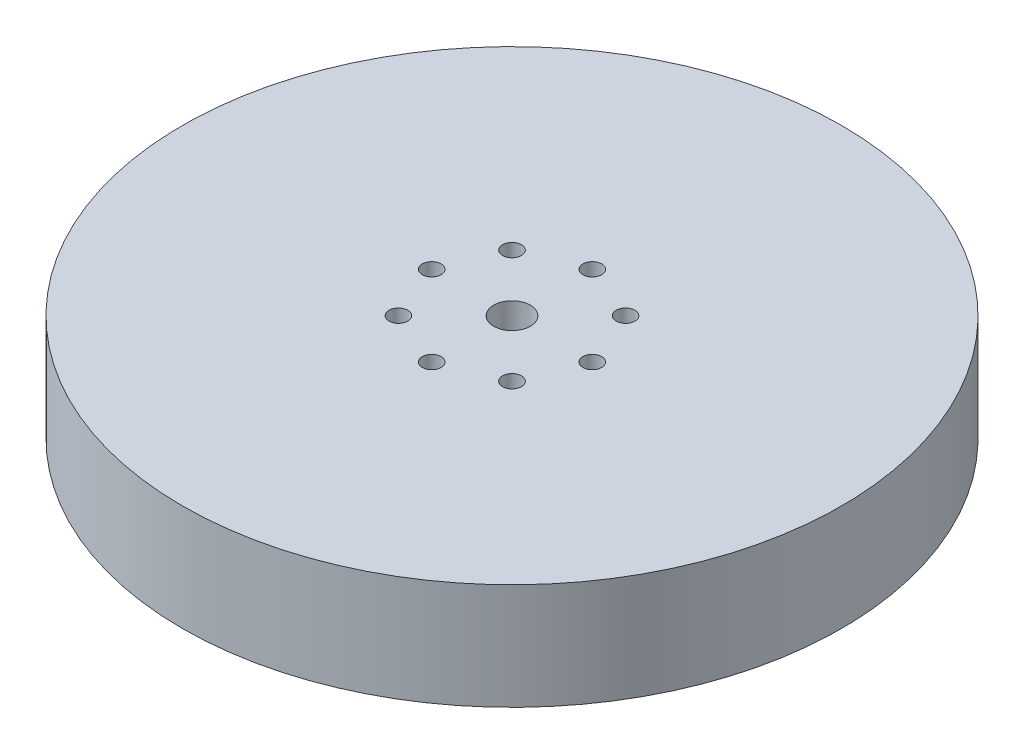
SolidWorks part; units mm, degrees
ref_plane "Front Plane" through (0, 0, 0) normal (0, 0, 1) x (1, 0, 0)
ref_plane "Top Plane" through (0, 0, 0) normal (0, 1, 0) x (1, 0, 0)
ref_plane "Right Plane" through (0, 0, 0) normal (1, 0, 0) x (0, 0, -1)
sketch "Sketch1" plane through (0, 0, 0) normal (0, 1, 0) x (1, 0, 0)
  circle A0 centre (0, 0) radius 90
  dimension "FLANGE_OD" = 180
extrude "Boss-Extrude1" add sketch "Sketch1" along normal blind 29
sketch "Sketch2" plane through (0, 0, 0) normal (0, 1, 0) x (1, 0, 0)
  circle A0 centre (0, 0) radius 5
  dimension "BORE_D" = 10
extrude "Cut-Extrude1" cut sketch "Sketch2" along normal through all
sketch "Sketch3" plane through (0, 29, 0) normal (0, 1, 0) x (1, 0, 0)
  circle A0 centre (0, 0) radius 21.9273 construction
  circle A1 centre (-21.9273, 0) radius 2.5711
  dimension "BOLT_D" = 5.1422
  dimension "BOLT_PCD" = 43.8546
extrude "Cut-Extrude2" cut sketch "Sketch3" against normal blind 17.9259
pattern_circular "CirPattern1" count 8 over 360 about axis through (0, 0, 0) along (0, 1, 0) of "Cut-Extrude2"
